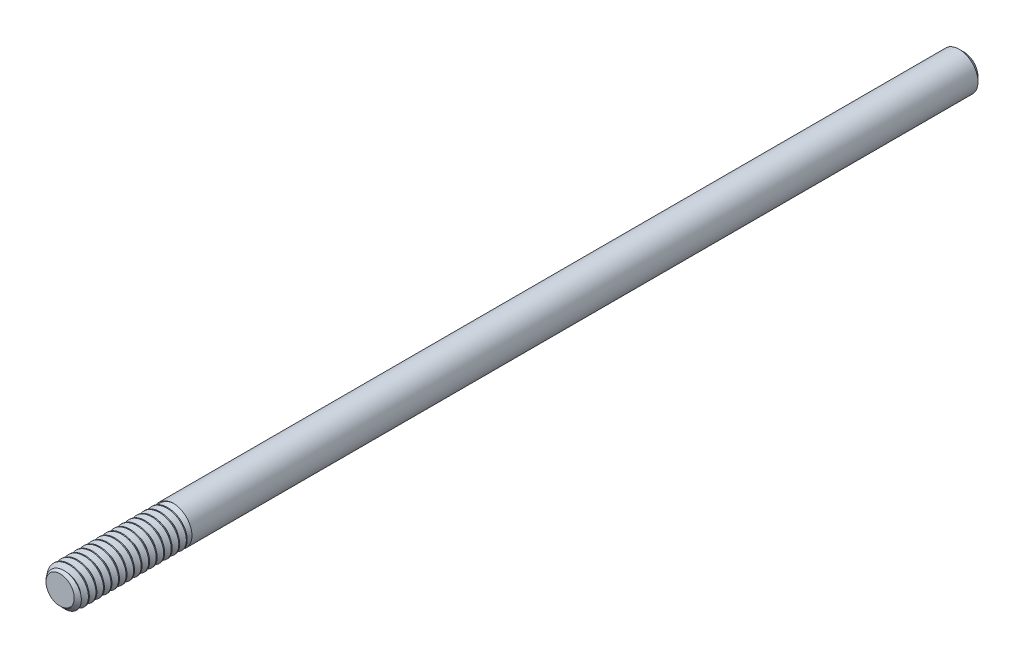
SolidWorks part; units mm, degrees
ref_plane "Front Plane" through (0, 0, 0) normal (0, 0, 1) x (1, 0, 0)
ref_plane "Top Plane" through (0, 0, 0) normal (0, 1, 0) x (1, 0, 0)
ref_plane "Right Plane" through (0, 0, 0) normal (1, 0, 0) x (0, 0, -1)
sketch "Sketch1" plane through (0, 0, 0) normal (1, 0, 0) x (0, 0, -1)
  line L0 (-76.2, 0) -> (76.2, 0) construction
  line L1 (76.2, 3.175) -> (76.2, -3.175) construction
  line L2 (-76.2, 3.175) -> (-76.2, -3.175) construction
  line L3 (-57.15, 3.175) -> (-57.15, -3.175) construction
  line L4 (-76.2, 3.175) -> (-74.93, 3.175) construction
  line L5 (-76.2, -3.175) -> (-73.025, -3.175) construction
  point P4 (76.2, 0)
  point P7 (-76.2, 0)
  point P8 (0, 0)
  point P11 (-57.15, 0)
  point P13 (-57.15, 0)
  point P17 (-73.025, -3.175)
  dimension "Length" = 152.4
  dimension "Thread Dia" = 6.35
  dimension "Shaft Dia" = 6.35
  dimension "Thread Length" = 19.05
  dimension "Shaft Length" = 133.35
  dimension "Pitch" = 1.27
  dimension "D1" = 3.175
sketch "Sketch2" plane through (0, 0, 0) normal (0, 0, 1) x (1, 0, 0)
  line L0 (-3.175, 0) -> (3.175, 0) construction
  line L1 (0, 3.175) -> (0, -3.175) construction
  circle A0 centre (0, 0) radius 3.175 construction
  point P9 (0, 0)
  dimension "Shaft Dia" = 6.35
sketch "Sketch3" plane through (0, 0, 0) normal (1, 0, 0) x (0, 0, -1)
  line L0 (-76.2, 0) -> (76.2, 0)
  line L1 (76.2, 0) -> (76.2, 3.175)
  line L2 (76.2, 3.175) -> (-76.2, 3.175) construction
  line L3 (-76.2, 3.175) -> (-76.2, 0)
  line L4 (-76.2, 3.175) -> (-57.15, 3.175)
  line L5 (-57.15, 3.175) -> (76.2, 3.175)
revolve "Revolve1" add sketch "Sketch3" angle 360 about L0
chamfer "Chamfer1" distance 0.7937 angle 45 1 edges at (0, -3.175, 76.2)
chamfer "Chamfer2" distance 0.7937 angle 45 1 edges at (0, -3.175, -76.2)
ref_plane "Plane1" through (0, 0, 57.15) normal (0, 0, 1) x (1, 0, 0)
sketch "Sketch4" plane through (0, 0, 76.2) normal (0, 0, 1) x (1, 0, 0)
  circle A0 centre (0, 0) radius 3.175
curve "Helix/Spiral1" pitch 1.27 height 20.32 radius 3.175 centre (0, 0, 76.2) axis (0, 0, -1) start towards (0, 1, 0)
split "Split1" trim tools "Plane1" bodies to split 104 resulting bodies 105 106
sketch "Sketch5" plane through (0, 0, 0) normal (1, 0, 0) x (0, 0, -1)
  line L0 (-77.3906, 3.3125) -> (-76.1206, 3.3125) construction
  line L1 (-76.1206, 3.3125) -> (-76.7556, 2.2126) construction
  line L2 (-76.7556, 2.2126) -> (-77.3906, 3.3125) construction
  line L3 (-77.3509, 3.2437) -> (-76.1603, 3.2437) construction
  line L4 (-77.3113, 3.175) -> (-76.2, 3.175) construction
  line L5 (-76.835, 2.3501) -> (-76.6762, 2.3501) construction
  line L6 (-76.7556, 2.3501) -> (-76.7556, 2.2126) construction
  line L7 (-76.7556, 3.175) -> (-76.7556, 3.3125) construction
  line L8 (-77.3509, 3.2437) -> (-76.1603, 3.2437)
  line L9 (-76.1603, 3.2437) -> (-76.6762, 2.3501)
  line L10 (-76.6762, 2.3501) -> (-76.835, 2.3501)
  line L11 (-76.835, 2.3501) -> (-77.3509, 3.2437)
  point P12 (-76.7556, 3.2437)
  dimension "D1" = 1.27
  dimension "D2" = 0.1588
sweep "Cut-Sweep1" cut profiles "Sketch5" path "Helix/Spiral1" align with end faces yes
sketch "Sketch6" plane through (0, 0, 57.15) normal (0, 0, 1) x (1, 0, 0)
  circle A1 centre (0, 0) radius 3.175
  circle A2 centre (0, 0) radius 3.175
  dimension "D1" = 0
extrude "Boss-Extrude1" add sketch "Sketch6" along normal through all draft 30
equation "\"D1@Chamfer1\"=\"Thread Dia@Sketch1\"*.125"
equation "\"D1@Chamfer2\"=\"Shaft Dia@Sketch1\"*.125"
equation "\"D3@Helix/Spiral1\"=\"Thread Length@Sketch1\"+\"Pitch@Sketch1\""
equation "\"D4@Helix/Spiral1\"=\"Pitch@Sketch1\""
equation "\"D2@Sketch5\"=\"D1@Sketch5\"/8"
equation "\"D1@Sketch5\"=\"Pitch@Sketch1\""
equation "\"D1@Sketch1\"=\"Pitch@Sketch1\"*2.5"
